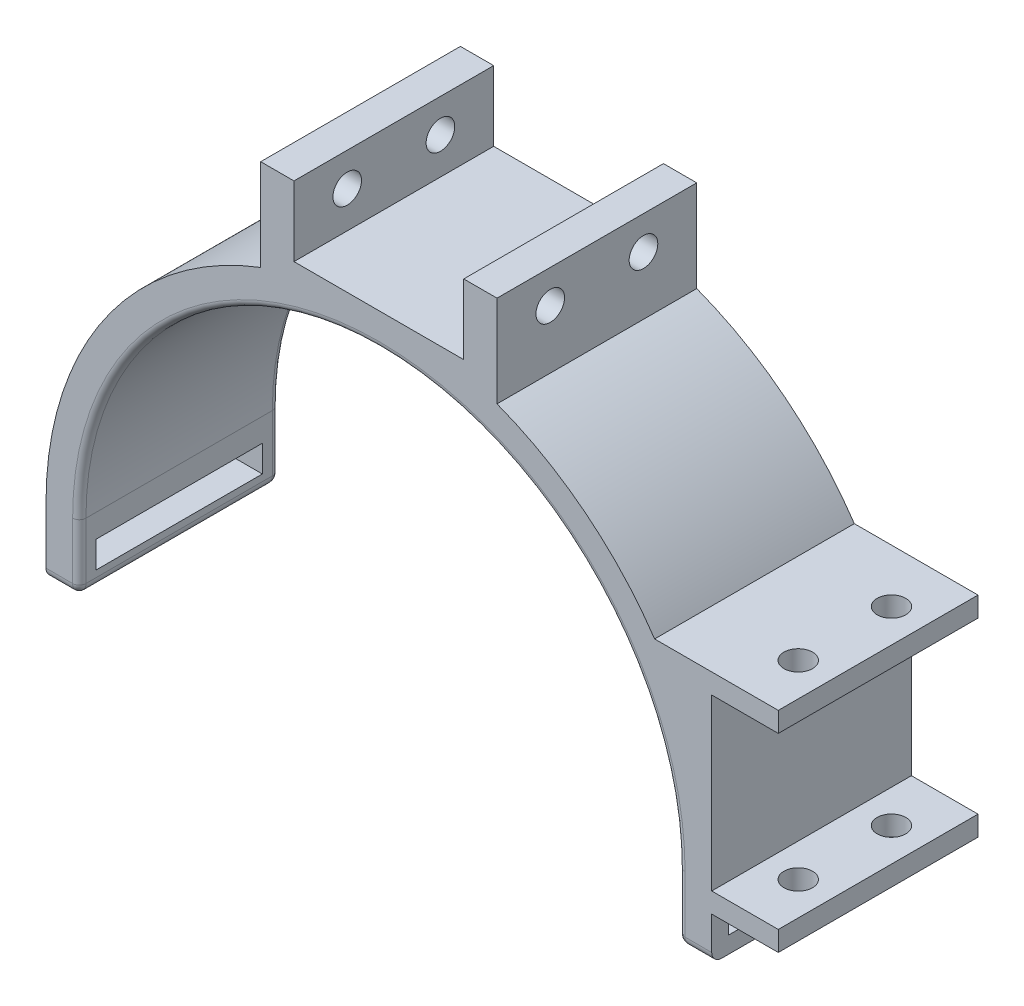
SolidWorks part; units mm, degrees
ref_plane "Front Plane" through (0, 0, 0) normal (0, 0, 1) x (1, 0, 0)
ref_plane "Top Plane" through (0, 0, 0) normal (0, 1, 0) x (1, 0, 0)
ref_plane "Right Plane" through (0, 0, 0) normal (1, 0, 0) x (0, 0, -1)
sketch "Sketch1" plane through (0, 0, 0) normal (0, 0, 1) x (1, 0, 0)
  line L0 (0, 0) -> (90, 0) construction
  line L1 (45, 45) -> (45, 0) construction
  line L2 (0, 0) -> (-5, 0)
  line L3 (90, 0) -> (95, 0)
  line L4 (45, 50) -> (45, 45) construction
  line L5 (95, -10) -> (90, -10)
  line L6 (-5, 0) -> (0, 0)
  line L7 (-5, 0) -> (-5, -10)
  line L8 (-5, -10) -> (0, -10)
  line L9 (0, 0) -> (0, -10)
  line L10 (90, 0) -> (90, -10)
  line L11 (95, 0) -> (90, 0)
  line L12 (95, 0) -> (95, -10)
  arc A0 (0, 0) -> (90, 0) centre (45, 0) cw
  arc A1 (-5, 0) -> (95, 0) centre (45, 0) cw
  dimension "D1" = 90
  dimension "D2" = 45
  dimension "D3" = 5
  dimension "D4" = 5
  dimension "D5" = 10
extrude "Boss-Extrude1" add sketch "Sketch1" along normal blind 30 contours A1 L2 A0 L3 | L12 L3 L10 L5 | L9 L2 L7 L8 region at (-2.5, -5, 0) region at (-2.5, 1.118, 0) region at (92.5, -5, 0)
sketch "Sketch2" plane through (0, 0, 30) normal (0, 0, 1) x (1, 0, 0)
  line L0 (45, 50) -> (45, 45) construction
  line L1 (57.75, 45) -> (57.75, 50)
  line L6 (57.75, 45) -> (32.25, 45)
  line L7 (45, 45) -> (45, 50)
  line L8 (57.75, 50) -> (32.25, 50)
  line L9 (32.25, 45) -> (32.25, 50)
  line L10 (32.25, 45) -> (27.25, 45)
  line L11 (32.25, 45) -> (32.25, 60.5)
  line L12 (32.25, 60.5) -> (27.25, 60.5)
  line L13 (27.25, 45) -> (27.25, 60.5)
  line L14 (57.75, 60.5) -> (62.75, 60.5)
  line L15 (62.75, 45) -> (62.75, 60.5)
  line L16 (57.75, 45) -> (62.75, 45)
  line L17 (57.75, 45) -> (57.75, 60.5)
  line L19 (27.25, 60.5) -> (62.75, 60.5)
  line L20 (27.25, 60.5) -> (27.25, 63.5)
  line L21 (27.25, 63.5) -> (62.75, 63.5)
  line L22 (62.75, 60.5) -> (62.75, 63.5)
  arc A0 (95, 0) -> (-5, 0) centre (45, 0) ccw construction
  arc A1 (90, 0) -> (0, 0) centre (45, 0) ccw construction
  arc M12 (95, 0) -> (-5, 0) centre (45, 0) ccw
  dimension "D1" = 12.75
  dimension "D2" = 5
  dimension "D3" = 10.5
  dimension "D4" = 3
extrude "Boss-Extrude2" add sketch "Sketch2" against normal blind 30 contours L13 L9 L11 L12 M12 | L9 L8 M12 | L9 L6 L7 M12 | L7 L6 L1 M12 | L1 L8 M12 | L17 L1 L15 L14 M12 | L13 L10 L9 M12 | L1 L16 L15 M12 region at (50.9819, 47.2535, 30) region at (59.9925, 46.3381, 30) region at (54.5731, 49.5056, 30) region at (60.3017, 54.0384, 30) region at (39.0181, 47.2535, 30) region at (35.4269, 49.5056, 30) region at (30.0075, 46.3381, 30) region at (29.6983, 54.0384, 30)
sketch "Sketch3" plane through (95, 0, 0) normal (1, 0, 0) x (0, 0, -1)
  line L0 (0, 0) -> (0, -10) construction
  line L1 (-27.5, -3.5) -> (-2.5, -3.5)
  line L2 (-27.5, -3.5) -> (-27.5, -7.5)
  line L3 (-27.5, -7.5) -> (-2.5, -7.5)
  line L4 (-2.5, -3.5) -> (-2.5, -7.5)
  line L5 (-30, 0) -> (-30, -10) construction
  line L6 (-30, -10) -> (0, -10) construction
  dimension "D1" = 2.5
  dimension "D2" = 2.5
  dimension "D3" = 2.5
  dimension "D4" = 4
extrude "Cut-Extrude1" cut sketch "Sketch3" against normal through all
sketch "Sketch4" plane through (95, 0, 0) normal (1, 0, 0) x (0, 0, -1)
  line L0 (-2.5, -3.5) -> (0, -3.5) construction
  line L1 (0, 0) -> (0, -10) construction
  line L2 (-30, 46.7433) -> (-30, 0) construction
  line L3 (0, -3.5) -> (-30, -3.5)
  line L4 (0, -3.5) -> (0, 28)
  line L5 (0, 28) -> (-30, 28)
  line L6 (-30, -3.5) -> (-30, 28)
  dimension "D1" = 31.5
extrude "Boss-Extrude3" add sketch "Sketch4" against normal up to next
sketch "Sketch5" plane through (95, 0, 0) normal (1, 0, 0) x (0, 0, -1)
  line L0 (-2.5, -3.5) -> (0, -3.5) construction
  line L1 (0, 28) -> (0, -10) construction
  line L2 (-30, 28) -> (-30, -10) construction
  line L3 (0, -3.5) -> (-30, -3.5)
  line L4 (0, -3.5) -> (0, -0.5)
  line L5 (0, -0.5) -> (-30, -0.5)
  line L6 (-30, -3.5) -> (-30, -0.5)
  line L8 (0, 28) -> (-30, 28)
  line L9 (0, 28) -> (0, 25)
  line L10 (0, 25) -> (-30, 25)
  line L11 (-30, 28) -> (-30, 25)
  dimension "D1" = 3
  dimension "D2" = 3
extrude "Boss-Extrude4" add sketch "Sketch5" along normal blind 10
sketch "Sketch6" plane through (27.25, 0, 0) normal (-1, 0, 0) x (0, 0, 1)
  line L0 (30, 55.5) -> (0, 55.5) construction
  line L1 (30, 46.7433) -> (30, 60.5) construction
  line L2 (0, 46.7433) -> (0, 60.5) construction
  line L3 (0, 60.5) -> (30, 60.5) construction
  line L4 (15, 60.5) -> (15, 46.7433) construction
  line L5 (30, 46.7433) -> (0, 46.7433) construction
  circle A0 centre (22, 55.5) radius 2.15
  circle A1 centre (8, 55.5) radius 2.15
  dimension "D2" = 4.3
  dimension "D3" = 7
  dimension "D1" = 5
extrude "Cut-Extrude2" cut sketch "Sketch6" against normal through all
sketch "Sketch7" plane through (0, 28, 0) normal (0, 1, 0) x (1, 0, 0)
  line L0 (100, 0) -> (100, -30) construction
  line L3 (86.4246, 0) -> (105, 0) construction
  line L4 (86.4246, -30) -> (105, -30) construction
  line L5 (105, 0) -> (105, -30) construction
  line L6 (105, -15) -> (86.4246, -15) construction
  line L7 (86.4246, -30) -> (86.4246, 0) construction
  circle A0 centre (100, -22) radius 2.15
  circle A1 centre (100, -8) radius 2.15
  dimension "D2" = 4.3
  dimension "D3" = 7
  dimension "D1" = 5
extrude "Cut-Extrude3" cut sketch "Sketch7" against normal through all
fillet "Fillet1" radius 1 6 edges at (0, -5, 30) (90, -5, 30) (0, -5, 0) (90, -5, 0) (45, 45, 30) (45, 45, 0)
fillet "Fillet2" radius 1.5 10 edges at (93, -10, 30) (90.2929, -10, 29.7071) (93, -10, 0) (90.2929, -10, 0.2929) (-3, -10, 30) (-0.2929, -10, 29.7071) (-3, -10, 0) (-0.2929, -10, 0.2929) (90, -10, 15) (0, -10, 15)
